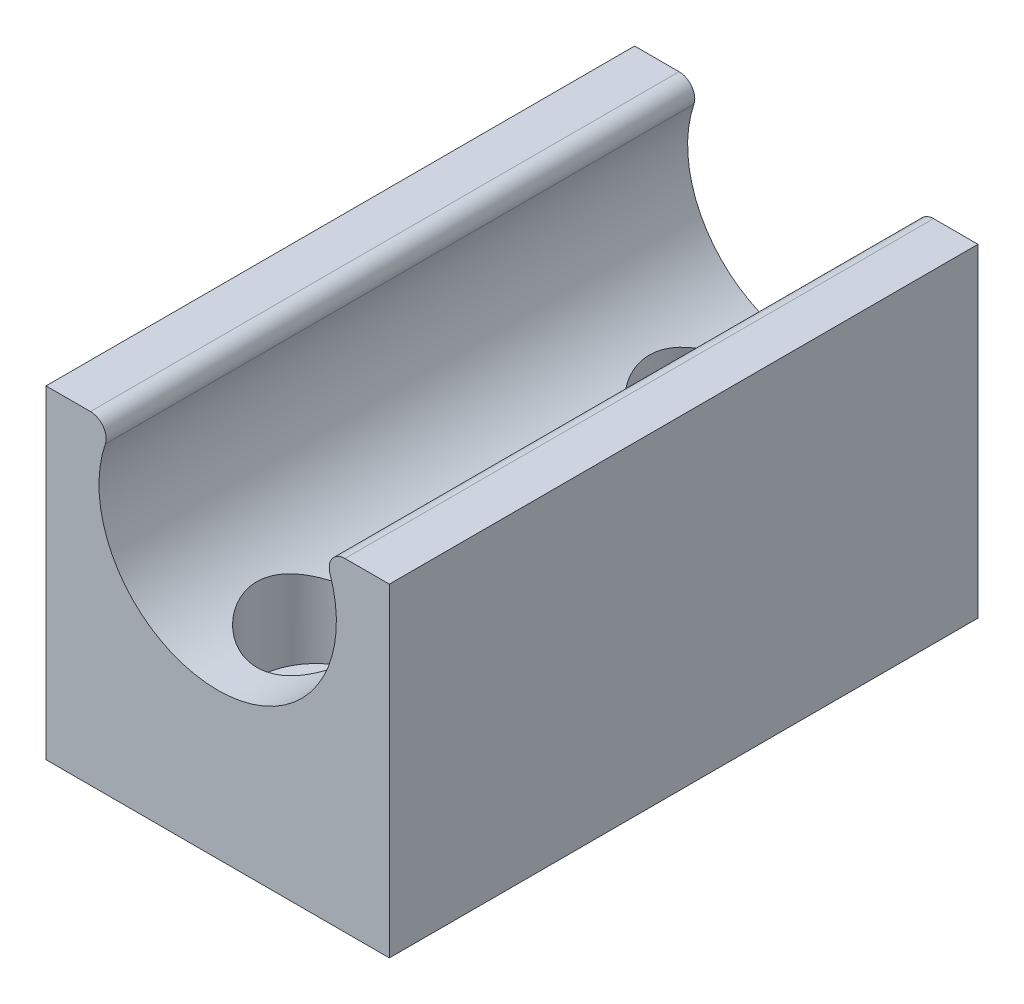
SolidWorks part; units mm, degrees
ref_plane "Front Plane" through (0, 0, 0) normal (0, 0, 1) x (1, 0, 0)
ref_plane "Top Plane" through (0, 0, 0) normal (0, 1, 0) x (1, 0, 0)
ref_plane "Right Plane" through (0, 0, 0) normal (1, 0, 0) x (0, 0, -1)
sketch "Sketch1" plane through (0, 0, 0) normal (0, 0, 1) x (1, 0, 0)
  line L0 (-5.25, 8.25) -> (-8.75, 8.25)
  line L1 (8.75, -8.25) -> (-8.75, -8.25)
  line L2 (8.75, -8.25) -> (8.75, 8.25)
  line L3 (8.75, 8.25) -> (5.25, 8.25)
  line L4 (-8.75, -8.25) -> (-8.75, 8.25)
  line L5 (8.75, -8.25) -> (-8.75, 8.25) construction
  line L6 (8.75, 8.25) -> (-8.75, -8.25) construction
  arc A0 (-5.25, 8.25) -> (5.25, 8.25) centre (0, 5.2433) ccw
  point P0 (0, 0)
  dimension "D1" = 12.1
  dimension "D2" = 3.5
  dimension "D3" = 17.5
  dimension "D4" = 16.5
extrude "Boss-Extrude1" add sketch "Sketch1" along normal blind 30
fillet "Fillet1" radius 0.8 2 edges at (5.25, 8.25, 15) (-5.25, 8.25, 15)
sketch "Sketch3" plane through (0, 8.25, 0) normal (0, 1, 0) x (1, 0, 0)
  line L0 (6.05, 0) -> (-6.05, 0) construction
  line L1 (-6.05, -30) -> (6.05, -30) construction
  circle A0 centre (0, -5) radius 3
  circle A1 centre (0, -25) radius 3
  dimension "D1" = 6
  dimension "D2" = 5
  dimension "D3" = 5
extrude "Cut-Extrude1" cut sketch "Sketch3" against normal blind 12.5
sketch "Sketch4" plane through (0, 8.25, 0) normal (0, 1, 0) x (1, 0, 0)
  circle A0 centre (0, -5) radius 1.55
  circle A1 centre (0, -25) radius 1.55
  dimension "D1" = 3.1
  dimension "D2" = 3.1
extrude "Cut-Extrude2" cut sketch "Sketch4" against normal through all
